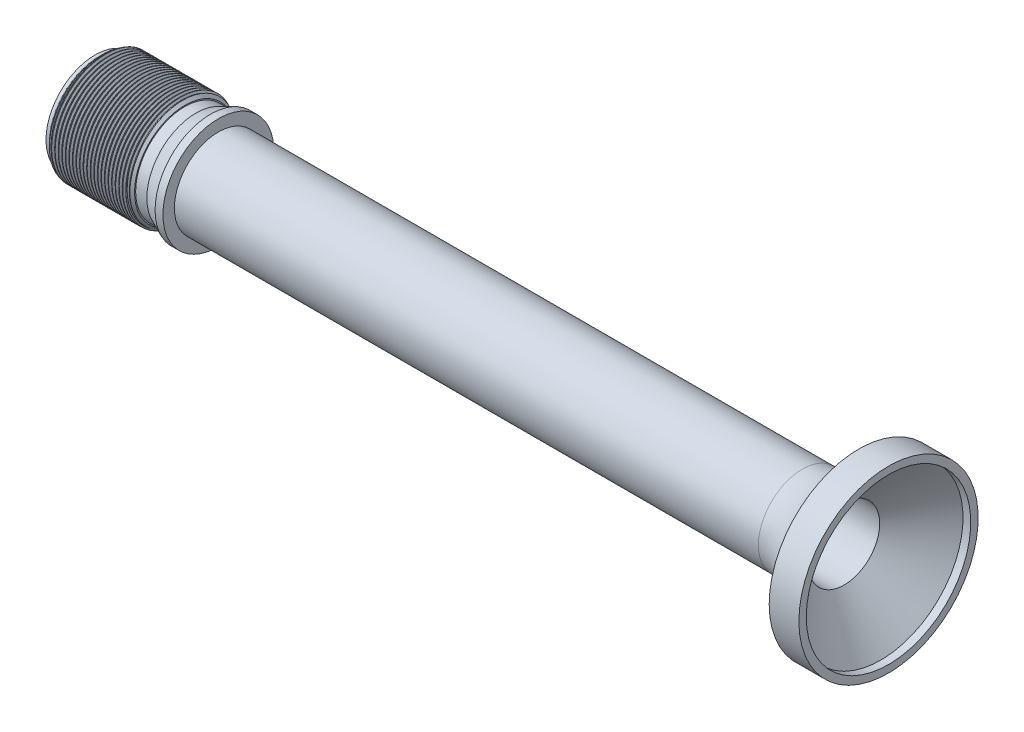
SolidWorks part; units mm, degrees
ref_plane "Front Plane" through (0, 0, 0) normal (0, 0, 1) x (1, 0, 0)
ref_plane "Top Plane" through (0, 0, 0) normal (0, 1, 0) x (1, 0, 0)
ref_plane "Right Plane" through (0, 0, 0) normal (1, 0, 0) x (0, 0, -1)
sketch "Sketch1" plane through (0, 0, 0) normal (0, 0, 1) x (1, 0, 0)
  line L0 (0, 0) -> (42.5195, 0) construction
  line L1 (0, 3.17) -> (66.8437, 3.17)
  line L3 (70.8, 7.34) -> (70.8, 8)
  line L4 (70.8, 8) -> (68.15, 8)
  line L5 (0, 3.17) -> (0, 4.86)
  line L7 (65.65, 3.925) -> (11, 3.925)
  line L8 (11, 3.925) -> (11, 4.95)
  line L9 (11, 4.95) -> (10.3, 4.95)
  line L10 (10.3, 4.95) -> (9, 4.3831)
  line L11 (9, 4.3831) -> (8, 4.3831)
  line L12 (8, 4.3831) -> (8, 4.86)
  line L13 (8, 4.86) -> (0, 4.86)
  line L15 (68.15, 8) -> (68.15, 7.34)
  line L16 (68.15, 7.34) -> (65.65, 3.925)
  line L17 (0, 4.3831) -> (0.5, 4.3831)
  line L18 (0.5, 4.3831) -> (0.5, 4.86)
  line L20 (70.8, 7.34) -> (70.1088, 7.34)
  line L21 (70.1088, 7.34) -> (66.8437, 3.17)
  point P5 (66.8437, 3.15)
  dimension "D1" = 2.65
  dimension "D2" = 0.66
  dimension "D3" = 8
  dimension "D4" = 3.17
  dimension "D5" = 3.925
  dimension "D6" = 4.95
  dimension "D7" = 4.86
  dimension "D8" = 9
  dimension "D9" = 1
  dimension "D10" = 11
  dimension "D11" = 0.7
  dimension "D12" = 70.8
  dimension "D13" = 2.5
  dimension "D14" = 0.5
revolve "Revolve1" add sketch "Sketch1" angle 360 about L0 region at (0.7096, 3.7765, 0)
fillet "Fillet1" radius 5 1 edges at (65.65, 0, 3.925)
chamfer "Chamfer1" distance 0.2 angle 45 1 edges at (8, 0, 4.86)
fillet "Fillet2" radius 0.2 1 edges at (0.5, 0, 4.3831)
thread "Thread1" pitch 0.3175 method cut profile "Thread Profile1" start angle 0, offset 0, length 8, pitch 0.3175, diameter 9.72
ref_plane "Plane1" through (0.5, 0, -4.86) normal (0, -1, 0) x (0, 0, -1)
sketch "Thread Profile1" plane through (0.5, 0, -4.86) normal (0, -1, 0) x (0, 0, -1)
  line L0 (0, 0) -> (0, 0.3175) construction
  line L11 (0, 0) -> (0, 0.2778)
  line L12 (0, 0.2778) -> (-0.1719, 0.1786)
  line L13 (-0.1719, 0.1786) -> (-0.1719, 0.0992)
  line L15 (-0.1719, 0.0992) -> (0, 0)
  line L17 (-0.1719, 0.1389) -> (0, 0.1389) construction
  point P2 (0, 0)
  dimension "Pitch" = 0.3175
  dimension "Profile_Angle" = 60
  dimension "Profile_Land" = 0.0794
  dimension "Profile_Height" = 0.1719
chamfer "Chamfer4" distance 0.1 angle 45 1 edges at (0, 0, 3.17)
sketch "Sketch4" plane through (0, 0, 0) normal (0, 1, 0) x (1, 0, 0)
  line L0 (0.3, 4.3831) -> (1.6011, 5.6841)
  line L1 (1.6011, 5.6841) -> (0.3, 5.6841)
  line L2 (0.3, 5.6841) -> (0.3, 4.3831)
  line L3 (0.3, 4.3831) -> (0, 4.3831) construction
  line L4 (0, 0) -> (-6.7226, 0) construction
  line L5 (8.1, 4.3831) -> (6.7989, 5.6841)
  line L6 (9, 4.3831) -> (8, 4.3831) construction
  line L7 (6.7989, 5.6841) -> (8.1, 5.6841)
  line L8 (8.1, 5.6841) -> (8.1, 4.3831)
  dimension "D1" = 45
  dimension "D2" = 45
  dimension "D3" = 7.8
revolve "Cut-Revolve1" cut sketch "Sketch4" angle 360 about L4
